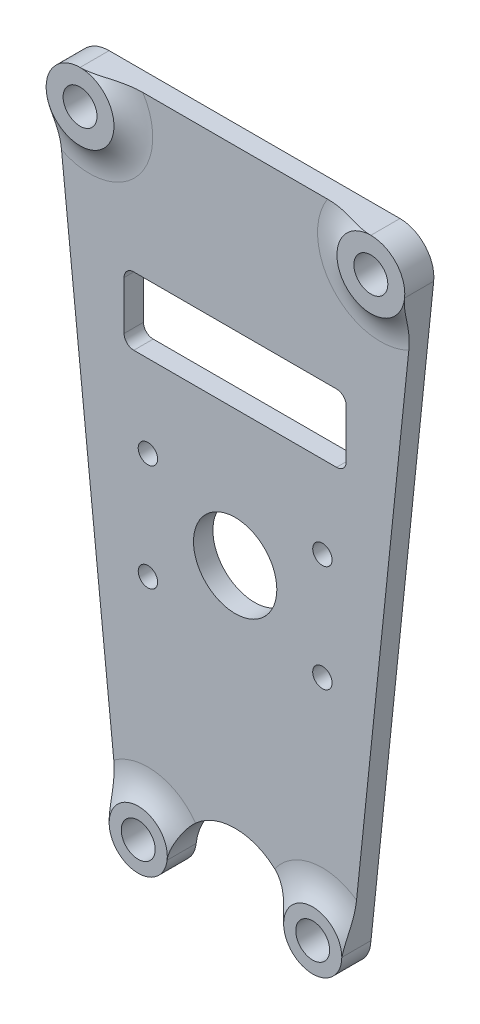
SolidWorks part; units mm, degrees
ref_plane "Front Plane" through (0, 0, 0) normal (0, 0, 1) x (1, 0, 0)
ref_plane "Top Plane" through (0, 0, 0) normal (0, 1, 0) x (1, 0, 0)
ref_plane "Right Plane" through (0, 0, 0) normal (1, 0, 0) x (0, 0, -1)
sketch "Sketch1" plane through (0, 0, 0) normal (0, 0, 1) x (1, 0, 0)
  line L0 (0, 40.1818) -> (0, -56.3497) construction
  line L1 (-15, 37.5) -> (15, 37.5)
  line L2 (-9, -31.5) -> (9, -31.5)
  line L3 (-18.4812, 33.6378) -> (-11.9839, -28.8105)
  line L4 (18.4812, 33.6378) -> (11.9839, -28.8105)
  line L5 (-9.8335, 0) -> (11.9839, 0) construction
  circle A0 centre (0, 0) radius 4.2982
  circle A1 centre (15, 34) radius 1.75
  circle A2 centre (-15, 34) radius 1.75
  circle A3 centre (9, -28.5) radius 1.75
  circle A4 centre (-9, -28.5) radius 1.75
  arc A5 (-15, 37.5) -> (-18.4812, 33.6378) centre (-15, 34) ccw
  arc A6 (18.4812, 33.6378) -> (15, 37.5) centre (15, 34) ccw
  arc A7 (9, -31.5) -> (11.9839, -28.8105) centre (9, -28.5) ccw
  arc A8 (-11.9839, -28.8105) -> (-9, -31.5) centre (-9, -28.5) ccw
  circle A9 centre (9, -5.5) radius 1
  circle A10 centre (-9, -5.5) radius 1
  circle A11 centre (9, 5.5) radius 1
  circle A12 centre (-9, 5.5) radius 1
  dimension "D1" = 34
  dimension "D2" = 15
  dimension "D3" = 3.5
  dimension "D4" = 3.5
  dimension "D5" = 9
  dimension "D6" = 28.5
  dimension "D7" = 7
  dimension "D8" = 7
  dimension "D9" = 6
  dimension "D10" = 6
  dimension "D11" = 2
  dimension "D12" = 9
  dimension "D13" = 5.5
extrude "Boss-Extrude1" add sketch "Sketch1" along normal blind 2
sketch "Sketch2" plane through (0, 0, 2) normal (0, 0, 1) x (1, 0, 0)
  line L1 (-11.4578, 21) -> (11.4578, 21)
  line L2 (-11.4578, 21) -> (-11.4578, 14)
  line L3 (-11.4578, 14) -> (11.4578, 14)
  line L4 (11.4578, 21) -> (11.4578, 14)
  line L5 (-11.4578, 21) -> (11.4578, 14) construction
  line L6 (-11.4578, 14) -> (11.4578, 21) construction
  point P0 (0, 17.5)
  dimension "D1" = 14
  dimension "D2" = 7
extrude "Cut-Extrude1" cut sketch "Sketch2" against normal blind 2
fillet "Fillet1" radius 1 4 edges at (11.4578, 21, 1) (11.4578, 14, 1) (-11.4578, 14, 1) (-11.4578, 21, 1)
sketch "Sketch3" plane through (0, 0, 2) normal (0, 0, 1) x (1, 0, 0)
  circle A0 centre (-15, 34) radius 3.5
  circle A1 centre (15, 34) radius 3.5
  circle A2 centre (9, -28.5) radius 3
  circle A3 centre (-9, -28.5) radius 3
  circle A4 centre (-9, -28.5) radius 1.75
  circle A5 centre (9, -28.5) radius 1.75
  circle A6 centre (15, 34) radius 1.75
  circle A7 centre (-15, 34) radius 1.75
extrude "Boss-Extrude2" add sketch "Sketch3" along normal blind 1
sketch "Sketch4" plane through (0, 0, 2) normal (0, 0, 1) x (1, 0, 0)
  line L0 (-12, -28.5) -> (-13.7582, -28.5)
  line L1 (-13.7582, -28.5) -> (-13.7582, -33.7066)
  line L2 (-13.7582, -33.7066) -> (14.3775, -33.7066)
  line L3 (14.3775, -33.7066) -> (14.3775, -28.5)
  line L4 (14.3775, -28.5) -> (12, -28.5)
  arc A0 (-6.0197, -28.843) -> (6.0197, -28.843) centre (0, -29.5359) cw
  arc A1 (-9, -31.5) -> (-11.9839, -28.8105) centre (-9, -28.5) ccw construction
  circle A2 centre (9, -28.5) radius 3 construction
  circle A3 centre (-9, -28.5) radius 3 construction
  arc A4 (11.9839, -28.8105) -> (9, -31.5) centre (9, -28.5) ccw construction
  arc A5 (-6.0197, -28.843) -> (-12, -28.5) centre (-9, -28.5) cw
  arc A6 (6.0197, -28.843) -> (12, -28.5) centre (9, -28.5) ccw
extrude "Cut-Extrude2" cut sketch "Sketch4" against normal through all
fillet "Fillet2" radius 5 4 edges at (12.4002, 31.6567, 2) (-12.4002, 31.6567, 2) (8.8282, -25.5049, 2) (-8.8282, -25.5049, 2)
